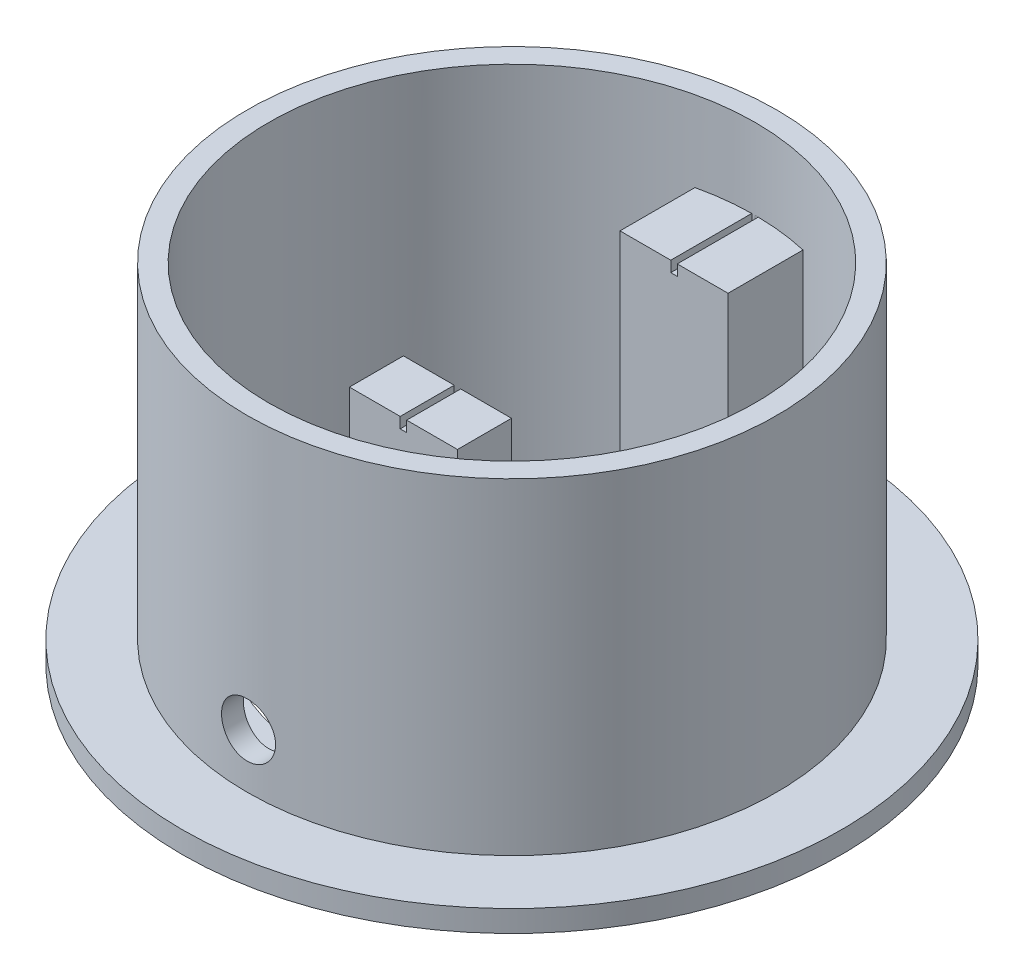
SolidWorks part; units mm, degrees
ref_plane "Front Plane" through (0, 0, 0) normal (0, 0, 1) x (1, 0, 0)
ref_plane "Top Plane" through (0, 0, 0) normal (0, 1, 0) x (1, 0, 0)
ref_plane "Right Plane" through (0, 0, 0) normal (1, 0, 0) x (0, 0, -1)
sketch "Sketch1" plane through (0, 0, 0) normal (0, 1, 0) x (1, 0, 0)
  line L0 (0, 37) -> (0, -37) construction
  line L1 (10, -10.08) -> (-10, -10.08)
  line L2 (10, -10.08) -> (10, -20.08)
  line L3 (-10, 30) -> (10, 30)
  line L4 (-10, -10.08) -> (-10, -20.08)
  line L5 (-10, -20.08) -> (10, -20.08)
  line L6 (10, -10.08) -> (31.6928, -31.9463)
  line L7 (-10, -10.08) -> (-31.6928, -31.9463)
  line L8 (-15, -23.2538) -> (15, -23.2538)
  line L9 (-15, -23.2538) -> (-21.6775, -29.9848)
  line L10 (15, -23.2538) -> (21.6775, -29.9848)
  line L11 (10, 30) -> (10, 43.8748)
  line L12 (-10, 30) -> (-10, 43.8748)
  circle A0 centre (0, 0) radius 61
  circle A1 centre (0, 0) radius 49
  circle A2 centre (0, 0) radius 45
  arc A3 (-21.6775, -29.9848) -> (21.6775, -29.9848) centre (0, 0) ccw
  circle A4 centre (0, 0) radius 6
  point P16 (0, -20.08)
  point P17 (0, -10.08)
  point P19 (0, 30)
  point P22 (0, -23.2538)
  dimension "D1" = 122
  dimension "D2" = 98
  dimension "D3" = 90
  dimension "D4" = 74
  dimension "D5" = 12
  dimension "D6" = 10.08
  dimension "D7" = 40.08
  dimension "D8" = 10
  dimension "D9" = 30
extrude "Boss-Extrude1" add sketch "Sketch1" along normal blind 4 contours A0 A1 region at (-59.2747, 0, 0)
extrude "Boss-Extrude2" add sketch "Sketch1<4>" along normal blind 4 separate body contours L7 A2 L6 L2 L5 L8 L10 A3 L9 L4 region at (20.3326, 0, 21.5228)
sketch "Sketch1<4>" plane through (0, 0, 0) normal (0, 1, 0) x (1, 0, 0) same geometry as "Sketch1"
extrude "Boss-Extrude3" add sketch "Sketch1<5>" along normal blind 64.4 contours A1 A2 region at (-47.6141, 0, 0)
sketch "Sketch1<5>" plane through (0, 0, 0) normal (0, 1, 0) x (1, 0, 0) same geometry as "Sketch1"
extrude "Boss-Extrude4" add sketch "Sketch1<8>" along normal blind 49.5 contours L1 L0 L5 L2 | L0 L1 L4 L5 | L11 A2 L12 L3 region at (0, 0, -37.3173) region at (5, 0, 15.08) region at (-5, 0, 15.08)
sketch "Sketch1<8>" plane through (0, 0, 0) normal (0, 1, 0) x (1, 0, 0) same geometry as "Sketch1"
sketch "Sketch2" plane through (0, 0, 10.08) normal (0, 0, -1) x (-1, 0, 0)
  line L27 (-10, 0) -> (10, 0)
  line L28 (10, 0) -> (10, 4)
  line L29 (10, 4) -> (10, 49.5)
  line L30 (10, 49.5) -> (-10, 49.5)
  line L31 (-10, 49.5) -> (-10, 4)
  line L32 (-10, 4) -> (-10, 0)
  line L33 (-10, 0) -> (10, 0)
  line L34 (10, 0) -> (10, 4)
  line L35 (10, 4) -> (10, 49.5)
  line L36 (10, 49.5) -> (-10, 49.5)
  line L37 (-10, 49.5) -> (-10, 4)
  line L38 (-10, 4) -> (-10, 0)
  line L39 (-5, 29) -> (5, 29)
  line L45 (-5, 5) -> (5, 5)
  line L46 (5, 5) -> (5, 44.5)
  line L47 (5, 44.5) -> (-5, 44.5)
  line L48 (-5, 44.5) -> (-5, 5)
  line L49 (-5, 5) -> (5, 5)
  line L50 (5, 5) -> (5, 44.5)
  line L51 (5, 44.5) -> (-5, 44.5)
  line L52 (-5, 44.5) -> (-5, 5)
  dimension "D3" = 24
  dimension "D1" = 0
  dimension "D2" = 5
extrude "Cut-Extrude1" cut sketch "Sketch2" against normal up to next contours L39 L52 L49 L50 region at (0, 17, 10.08)
sketch "Sketch3" plane through (0, 0, 10.08) normal (0, 0, -1) x (-1, 0, 0)
  line L0 (61, 4) -> (-61, 4) construction
  circle A0 centre (0, 14) radius 5
  dimension "D2" = 10
  dimension "D1" = 10
extrude "Cut-Extrude2" cut sketch "Sketch3" against normal up to next
sketch "Sketch4" plane through (0, 49.5, 0) normal (0, 1, 0) x (1, 0, 0)
  line L1 (-10, 30) -> (10, 30) construction
  line L2 (-0.6, 30) -> (0.6, 30)
  line L3 (0.6, 30) -> (0.6, 44.996)
  line L4 (0.6, 44.996) -> (0, 45)
  line L5 (-0.6, 30) -> (-0.6, 44.996)
  line L7 (0, -10.08) -> (0.6, -10.08)
  line L8 (0.6, -10.08) -> (0.6, -20.08)
  line L9 (-10, 30) -> (10, 30)
  line L10 (10, 30) -> (10, 43.8748)
  line L11 (-10, 43.8748) -> (-10, 30)
  line L12 (-10, 30) -> (10, 30)
  line L13 (10, 30) -> (10, 43.8748)
  line L14 (-10, 43.8748) -> (-10, 30)
  line L15 (-0.6, -10.08) -> (-0.6, -17.68)
  line L16 (10, -10.08) -> (-10, -10.08)
  line L17 (-10, -10.08) -> (-10, -20.08)
  line L18 (-10, -20.08) -> (10, -20.08)
  line L19 (10, -20.08) -> (10, -10.08)
  line L20 (10, -10.08) -> (-10, -10.08)
  line L21 (-10, -10.08) -> (-10, -20.08)
  line L22 (-10, -20.08) -> (10, -20.08)
  line L23 (10, -20.08) -> (10, -10.08)
  arc A0 (10, 43.8748) -> (-10, 43.8748) centre (0, 0) ccw construction
  circle A1 centre (0, 0) radius 45 construction
  arc A3 (10, 43.8748) -> (-10, 43.8748) centre (0, 0) ccw
  arc A4 (10, 43.8748) -> (-10, 43.8748) centre (0, 0) ccw
  line M14 (-10, 30) -> (10, 30)
  arc M16 (10, 43.8748) -> (-10, 43.8748) centre (0, 0) ccw
  dimension "D2" = 0
  dimension "D3" = 0
extrude "Cut-Extrude4" cut sketch "Sketch4" against normal blind 2 contours L5 L3 L4 M14 M16 region at (0, 49.5, -37.4992)
sketch "Sketch5" plane through (0, 49.5, 0) normal (0, 1, 0) x (1, 0, 0)
  line L1 (10, -10.08) -> (-10, -10.08) construction
  line L3 (0.6, -10.08) -> (0.6, -20.08)
  line L4 (-0.6, -10.08) -> (-0.6, -20.08)
  line L8 (10, -10.08) -> (-10, -10.08)
  line L9 (-10, -10.08) -> (-10, -20.08)
  line L10 (-10, -20.08) -> (10, -20.08)
  line L11 (10, -20.08) -> (10, -10.08)
  line L12 (10, -10.08) -> (-10, -10.08)
  line L13 (-10, -10.08) -> (-10, -20.08)
  line L14 (-10, -20.08) -> (10, -20.08)
  line L15 (10, -20.08) -> (10, -10.08)
  line M7 (10, -10.08) -> (-10, -10.08)
  line M9 (-10, -20.08) -> (10, -20.08)
  dimension "D2" = 0
extrude "Cut-Extrude5" cut sketch "Sketch5" against normal blind 2 contours L4 L3 M7 M9 region at (0, 49.5, 15.08)
